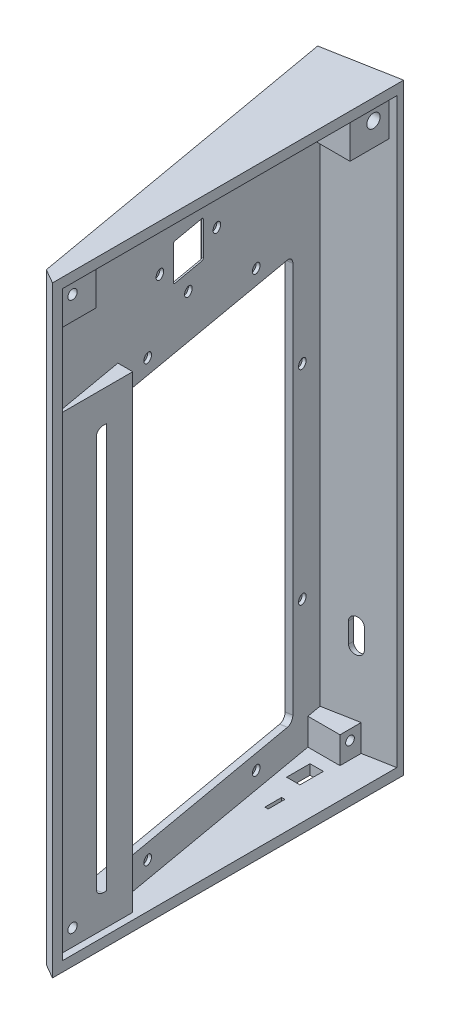
SolidWorks part; units mm, degrees
ref_plane "前视基准面" through (0, 0, 0) normal (0, 0, 1) x (1, 0, 0)
ref_plane "上视基准面" through (0, 0, 0) normal (0, 1, 0) x (1, 0, 0)
ref_plane "右视基准面" through (0, 0, 0) normal (1, 0, 0) x (0, 0, -1)
other "Configuration Table"
sketch "草图1" plane through (0, 0, 0) normal (0, 1, 0) x (1, 0, 0)
  line L0 (82.9035, -37.3993) -> (82.9035, -142.3993)
  line L1 (82.9035, -142.3993) -> (78.5734, -139.8993)
  line L2 (78.5734, -139.8993) -> (61.2086, -41.4185)
  line L3 (61.2086, -41.4185) -> (82.9035, -37.3993)
  dimension "D1" = 100
  dimension "D2" = 105
  dimension "D3" = 5
  dimension "D4" = 170
  dimension "D5" = 60
  dimension "D6" = 90.496
  dimension "D7" = 79.504
extrude "凸台-拉伸1" add sketch "草图1" along normal blind 180
sketch "草图5" plane through (52.2799, 0, -9.2184) normal (-0.9848, 0, 0.1736) x (0.1736, 0, 0.9848)
  line L0 (51.418, 180) -> (51.418, 0) construction
  line L1 (139.418, 12.5) -> (63.418, 12.5)
  line L2 (139.418, 12.5) -> (139.418, 133.5)
  line L3 (139.418, 133.5) -> (63.418, 133.5)
  line L4 (63.418, 12.5) -> (63.418, 133.5)
  line L5 (151.418, 180) -> (151.418, 0) construction
  line L6 (51.418, 0) -> (151.418, 0) construction
  dimension "D1" = 76
  dimension "D2" = 121
  dimension "D3" = 12
  dimension "D4" = 12
  dimension "D5" = 12.5
extrude "切除-拉伸2" cut sketch "草图5" against normal blind 2
sketch "草图7" plane through (82.9035, 0, 0) normal (1, 0, 0) x (0, 0, -1)
  line L8 (-139.3993, 3) -> (-40.3993, 3)
  line L9 (-40.3993, 3) -> (-40.3993, 177)
  line L10 (-40.3993, 177) -> (-139.3993, 177)
  line L11 (-139.3993, 177) -> (-139.3993, 3)
  line L12 (-139.3993, 3) -> (-40.3993, 3)
  line L13 (-40.3993, 3) -> (-40.3993, 177)
  line L14 (-40.3993, 177) -> (-139.3993, 177)
  line L15 (-139.3993, 177) -> (-139.3993, 3)
  dimension "D1" = 3
extrude "切除-拉伸3" cut sketch "草图7" against normal up to surface (19.8438 mm away) up to face at (71.8606, 73, 90.3116)
sketch "草图10" plane through (54.2496, 0, -9.5657) normal (0.9848, 0, -0.1736) x (-0.1736, 0, -0.9848)
  line L1 (-63.418, 12.5) -> (-59.918, 12.5) construction
  line L2 (-63.418, 12.5) -> (-63.418, 42.5) construction
  line L3 (-63.418, 42.5) -> (-59.918, 42.5) construction
  line L4 (-59.918, 12.5) -> (-59.918, 42.5) construction
  line L5 (-63.418, 133.5) -> (-59.918, 133.5) construction
  line L6 (-63.418, 133.5) -> (-63.418, 103.5) construction
  line L7 (-63.418, 103.5) -> (-59.918, 103.5) construction
  line L8 (-59.918, 133.5) -> (-59.918, 103.5) construction
  circle A0 centre (-59.918, 103.5) radius 1.4
  circle A1 centre (-59.918, 42.5) radius 1.4
  dimension "D1" = 30
  dimension "D2" = 30
  dimension "D3" = 3.5
  dimension "D4" = 3.5
extrude "切除-拉伸5" cut sketch "草图10" against normal blind 1
sketch "草图11" plane through (54.2496, 0, -9.5657) normal (0.9848, 0, -0.1736) x (-0.1736, 0, -0.9848)
  line L0 (-76.918, 8) -> (-116.918, 8) construction
  line L1 (-63.418, 133.5) -> (-76.918, 133.5) construction
  line L2 (-63.418, 133.5) -> (-63.418, 138) construction
  line L3 (-63.418, 138) -> (-76.918, 138) construction
  line L4 (-76.918, 133.5) -> (-76.918, 138) construction
  line L5 (-63.418, 12.5) -> (-76.918, 12.5) construction
  line L6 (-63.418, 12.5) -> (-63.418, 8) construction
  line L7 (-63.418, 8) -> (-76.918, 8) construction
  line L8 (-76.918, 12.5) -> (-76.918, 8) construction
  line L9 (-76.918, 138) -> (-116.918, 138) construction
  circle A0 centre (-116.918, 138) radius 1.4
  circle A1 centre (-76.918, 138) radius 1.4
  circle A2 centre (-116.918, 8) radius 1.4
  circle A3 centre (-76.918, 8) radius 1.4
  dimension "D1" = 13.5
  dimension "D2" = 4.5
  dimension "D3" = 13.5
  dimension "D4" = 4.5
  dimension "D5" = 40
  dimension "D6" = 40
extrude "切除-拉伸6" cut sketch "草图11" against normal blind 1
sketch "草图12" plane through (82.9035, 0, 0) normal (1, 0, 0) x (0, 0, -1)
  line L1 (-139.3993, 3) -> (-116.3993, 3)
  line L2 (-139.3993, 3) -> (-139.3993, 143)
  line L3 (-139.3993, 143) -> (-116.3993, 143)
  line L4 (-116.3993, 3) -> (-116.3993, 143)
  line L6 (-127.7343, 133.5) -> (-52.8889, 133.5) construction
  dimension "D1" = 9.5
  dimension "D2" = 23
extrude "凸台-拉伸3" add sketch "草图12" against normal up to surface (2.3874 mm away) up to face at (67.3631, 138, 64.8051)
sketch "草图13" plane through (54.2496, 0, -9.5657) normal (-0.9848, 0, 0.1736) x (0.1736, 0, 0.9848)
  line L4 (127.9081, 12.5) -> (139.418, 12.5)
  line L5 (139.418, 12.5) -> (139.418, 133.5)
  line L6 (139.418, 133.5) -> (127.9081, 133.5)
  line L7 (127.9081, 133.5) -> (127.9081, 12.5)
  line L8 (127.9081, 12.5) -> (139.418, 12.5)
  line L9 (139.418, 12.5) -> (139.418, 133.5)
  line L10 (139.418, 133.5) -> (127.9081, 133.5)
  line L11 (127.9081, 133.5) -> (127.9081, 12.5)
  dimension "D1" = 0
extrude "切除-拉伸7" cut sketch "草图13" against normal blind 2
sketch "草图14" plane through (52.2799, 0, -9.2184) normal (-0.9848, 0, 0.1736) x (0.1736, 0, 0.9848)
  line L0 (51.418, 180) -> (51.418, 0) construction
  line L1 (96.418, 151.5) -> (107.418, 151.5)
  line L2 (96.418, 151.5) -> (96.418, 162.5)
  line L3 (96.418, 162.5) -> (107.418, 162.5)
  line L4 (107.418, 151.5) -> (107.418, 162.5)
  line L5 (139.418, 133.5) -> (63.418, 133.5) construction
  line L6 (51.418, 180) -> (151.418, 180) construction
  dimension "D1" = 11
  dimension "D2" = 11
  dimension "D3" = 45
  dimension "D4" = 18
  dimension "D5" = 17.5
extrude "切除-拉伸8" cut sketch "草图14" against normal blind 2
sketch "草图17" plane through (9.4497, 0, 51.0074) normal (-0.1822, 0, -0.9833) x (-0.9833, 0, 0.1822)
  line L1 (-74.7037, 180) -> (-52.6396, 180)
  line L2 (-74.7037, 180) -> (-74.7037, 0)
  line L3 (-74.7037, 0) -> (-52.6396, 0)
  line L4 (-52.6396, 180) -> (-52.6396, 0)
extrude "凸台-拉伸9" add sketch "草图17" against normal blind 2
sketch "草图18" plane through (0, 0, 0) normal (0, -1, 0) x (1, 0, 0)
  line L0 (82.9035, 39.4333) -> (82.9035, 37.3993)
  line L1 (83.2679, 39.3658) -> (82.9035, 39.4333) construction
  line L2 (83.2679, 39.3658) -> (82.9035, 37.3993) construction
  line L3 (83.2679, 39.3658) -> (82.9035, 37.3993)
  line L4 (83.2679, 39.3658) -> (82.9035, 39.4333)
extrude "切除-拉伸9" cut sketch "草图18" against normal up to surface (180 mm away) up to face at (78.6267, 180, 73.3192)
sketch "草图19" plane through (0, 3, 0) normal (0, 1, 0) x (1, 0, 0)
  line L0 (82.9035, -40.3993) -> (82.9035, -36.7908) construction
  line L1 (77.596, -40.4166) -> (82.9035, -39.4333)
  line L2 (63.5225, -43.0238) -> (77.6894, -40.3993) construction
  line L3 (82.9035, -39.4333) -> (82.9035, -40.3993)
  line L4 (82.9035, -40.3993) -> (77.596, -40.4166)
extrude "切除-拉伸10" cut sketch "草图19" along normal up to surface (174 mm away) up to face at (77.507, 177, 80.5242)
sketch "草图20" plane through (82.9035, 0, 0) normal (1, 0, 0) x (0, 0, -1)
  line L1 (-139.3993, 143) -> (-116.3993, 143)
  line L2 (-139.3993, 143) -> (-139.3993, 3)
  line L3 (-139.3993, 3) -> (-116.3993, 3)
  line L4 (-116.3993, 143) -> (-116.3993, 3)
extrude "切除-拉伸11" cut sketch "草图20" against normal blind 2
sketch "草图21" plane through (54.2496, 0, -9.5657) normal (0.9848, 0, -0.1736) x (-0.1736, 0, -0.9848)
  line L0 (-107.418, 157) -> (-112.418, 157) construction
  line L1 (-107.418, 151.5) -> (-107.418, 162.5) construction
  line L2 (-101.918, 162.5) -> (-101.918, 167.5) construction
  line L3 (-107.418, 162.5) -> (-96.418, 162.5) construction
  line L4 (-96.418, 157) -> (-91.418, 157) construction
  line L5 (-96.418, 162.5) -> (-96.418, 151.5) construction
  line L6 (-101.918, 151.5) -> (-101.918, 146.5) construction
  line L7 (-96.418, 151.5) -> (-107.418, 151.5) construction
  circle A0 centre (-112.418, 157) radius 1.4
  circle A1 centre (-91.418, 157) radius 1.4
  circle A2 centre (-101.918, 146.5) radius 1.4
  circle A3 centre (-101.918, 167.5) radius 1.4
  dimension "D1" = 5
extrude "切除-拉伸12" cut sketch "草图21" against normal blind 1
sketch "草图23" plane through (80.9035, 0, 0) normal (1, 0, 0) x (0, 0, -1)
  line L0 (-51.4333, 8) -> (-51.4333, 26.4031) construction
  line L1 (-139.3993, 3) -> (-127.3993, 3)
  line L2 (-139.3993, 3) -> (-139.3993, 15)
  line L3 (-139.3993, 15) -> (-127.3993, 15)
  line L4 (-127.3993, 3) -> (-127.3993, 15)
  line L5 (-39.4333, 177) -> (-139.3993, 177) construction
  line L11 (-51.4333, 165) -> (-39.4333, 165)
  line L12 (-51.4333, 165) -> (-51.4333, 177)
  line L13 (-51.4333, 177) -> (-39.4333, 177)
  line L14 (-39.4333, 165) -> (-39.4333, 177)
  line L15 (-127.3993, 8) -> (-127.3993, 23.4787) construction
  line L17 (-127.3993, 165) -> (-139.3993, 165)
  line L18 (-127.3993, 165) -> (-127.3993, 177)
  line L19 (-127.3993, 177) -> (-139.3993, 177)
  line L20 (-139.3993, 165) -> (-139.3993, 177)
  dimension "D1" = 12
  dimension "D2" = 12
  dimension "D5" = 0
  dimension "D6" = 12
  dimension "D7" = 12
  dimension "D8" = 12
  dimension "D9" = 12
  dimension "D11" = 0
extrude "凸台-拉伸10" add sketch "草图23" against normal up to surface (0.3874 mm away) up to face at (73.5276, 157, 99.7657)
fillet "圆角4" radius 2 5 edges at (64.2772, 133.5, 53.0625) (78.4592, 133.5, 127.7343) (64.2772, 12.5, 53.0625) (77.4744, 12.5, 127.9079) (80.394, 12.5, 127.3931)
sketch "草图26" plane through (0, 177, 0) normal (0, 1, 0) x (1, 0, 0)
  line L3 (63.1752, -41.0542) -> (71.9242, -39.4333)
  line L4 (71.9242, -39.4333) -> (62.8894, -39.4333)
  line L5 (62.8894, -39.4333) -> (63.1752, -41.0542)
  line L6 (63.1752, -41.0542) -> (71.9242, -39.4333)
  line L7 (71.9242, -39.4333) -> (62.8894, -39.4333)
  line L8 (62.8894, -39.4333) -> (63.1752, -41.0542)
  dimension "D1" = 0
extrude "切除-拉伸15" cut sketch "草图26" against normal up to next
sketch "草图27" plane through (82.9035, 0, 0) normal (1, 0, 0) x (0, 0, -1)
  line L1 (-39.4333, 3) -> (-47.4333, 3)
  line L2 (-39.4333, 3) -> (-39.4333, 11)
  line L3 (-39.4333, 11) -> (-47.4333, 11)
  line L4 (-47.4333, 3) -> (-47.4333, 11)
  dimension "D1" = 8
  dimension "D2" = 8
extrude "凸台-拉伸11" add sketch "草图27" against normal up to surface (18.6035 mm away) up to face at (73.5276, 157, 99.7657)
sketch "草图28" plane through (82.9035, 0, 0) normal (1, 0, 0) x (0, 0, -1)
  line L1 (-47.4333, 3) -> (-39.4333, 3)
  line L2 (-47.4333, 3) -> (-47.4333, 11)
  line L3 (-47.4333, 11) -> (-39.4333, 11)
  line L4 (-39.4333, 3) -> (-39.4333, 11)
extrude "切除-拉伸16" cut sketch "草图28" against normal blind 9
sketch "草图29" plane through (0, 11, 0) normal (0, -1, 0) x (1, 0, 0)
  line L3 (73.9035, 41.1006) -> (73.9035, 39.4333)
  line L4 (73.9035, 39.4333) -> (82.9035, 39.4333)
  line L5 (82.9035, 39.4333) -> (73.9035, 41.1006)
  line L6 (73.9035, 41.1006) -> (73.9035, 39.4333)
  line L7 (73.9035, 39.4333) -> (82.9035, 39.4333)
  line L11 (82.9035, 39.4333) -> (73.9035, 41.1006)
  dimension "D1" = 0
extrude "凸台-拉伸12" add sketch "草图29" along normal up to surface (8 mm away) up to face at (77.0227, 3, 85.6663)
sketch "草图30" plane through (0, 3, 0) normal (0, -1, 0) x (1, 0, 0)
  line L3 (71.9242, 39.4333) -> (63.1752, 41.0542)
  line L4 (63.1752, 41.0542) -> (62.8894, 39.4333)
  line L5 (62.8894, 39.4333) -> (71.9242, 39.4333)
  line L6 (71.9242, 39.4333) -> (63.1752, 41.0542)
  line L7 (63.1752, 41.0542) -> (62.8894, 39.4333)
  line L8 (62.8894, 39.4333) -> (71.9242, 39.4333)
  dimension "D1" = 0
extrude "切除-拉伸17" cut sketch "草图30" against normal up to next
sketch "草图31" plane through (0, 0, 0) normal (0, -1, 0) x (1, 0, 0)
  line L1 (82.9035, 37.3993) -> (68.9035, 37.3993) construction
  line L2 (82.9035, 37.3993) -> (82.9035, 51.3993) construction
  line L3 (82.9035, 51.3993) -> (68.9035, 51.3993) construction
  line L4 (68.9035, 37.3993) -> (68.9035, 51.3993) construction
  line L5 (68.9035, 51.3993) -> (72.9035, 51.3993)
  line L6 (68.9035, 51.3993) -> (68.9035, 58.3993)
  line L7 (68.9035, 58.3993) -> (72.9035, 58.3993)
  line L8 (72.9035, 51.3993) -> (72.9035, 58.3993)
  dimension "D1" = 14
  dimension "D2" = 14
  dimension "D3" = 7
  dimension "D4" = 4
extrude "切除-拉伸18" cut sketch "草图31" against normal up to next
ref_plane "基准面1" through (0, 0, 37.3993) normal (0, 0, -1) x (-1, 0, 0)
ref_plane "基准面2" through (0, 0, 39.7193) normal (0, 0, -1) x (-1, 0, 0)
sketch "草图32" plane through (0, 0, 39.7193) normal (0, 0, -1) x (-1, 0, 0)
  line L0 (-72.7086, 36) -> (-72.7086, 30) construction
  line L1 (-70.7086, 36) -> (-70.7086, 30)
  line L2 (-74.7086, 36) -> (-74.7086, 30)
  line L3 (-82.9035, 180) -> (-61.2086, 180) construction
  line L4 (-61.2086, 180) -> (-61.2086, 0) construction
  arc A0 (-70.7086, 36) -> (-74.7086, 36) centre (-72.7086, 36) ccw
  arc A1 (-74.7086, 30) -> (-70.7086, 30) centre (-72.7086, 30) ccw
  point P2 (-72.7086, 33)
  point P9 (-72.7086, 28)
  point P10 (-72.7086, 38)
  dimension "D1" = 147
  dimension "D2" = 10
  dimension "D3" = 4
  dimension "D4" = 9.5
extrude "切除-拉伸23" cut sketch "草图32" against normal up to surface (1.9733 mm away) up to face at (75.3083, 89, 40.8404)
ref_plane "基准面4" through (0, 0, 40.2193) normal (0, 0, -1) x (-1, 0, 0)
sketch "草图35" plane through (0, 0, 40.2193) normal (0, 0, -1) x (-1, 0, 0)
  line L0 (-74.7086, 36) -> (-74.7086, 30) construction
  line L1 (-76.7086, 41) -> (-68.7086, 41)
  line L2 (-76.7086, 41) -> (-76.7086, 25)
  line L3 (-76.7086, 25) -> (-68.7086, 25)
  line L4 (-68.7086, 41) -> (-68.7086, 25)
  line L5 (-70.7086, 30) -> (-70.7086, 36) construction
  arc A0 (-70.7086, 36) -> (-74.7086, 36) centre (-72.7086, 36) ccw construction
  arc A1 (-74.7086, 30) -> (-70.7086, 30) centre (-72.7086, 30) ccw construction
  dimension "D1" = 5
  dimension "D2" = 5
  dimension "D3" = 2
  dimension "D4" = 2
extrude "切除-拉伸25" cut sketch "草图35" along normal up to surface (0.1902 mm away) up to face at (72.0561, 90, 39.4089)
fillet "圆角5" radius 0.5 4 edges at (76.7086, 25, 39.3831) (76.7086, 41, 39.3831) (68.7086, 25, 40.1241) (68.7086, 41, 40.1241)
sketch "草图36" plane through (0, 0, 0) normal (0, -1, 0) x (1, 0, 0)
  line L1 (82.9035, 37.3993) -> (74.4035, 37.3993) construction
  line L2 (82.9035, 37.3993) -> (82.9035, 64.3993) construction
  line L3 (82.9035, 64.3993) -> (74.4035, 64.3993) construction
  line L4 (74.4035, 37.3993) -> (74.4035, 64.3993) construction
  line L5 (74.4035, 64.3993) -> (73.4035, 64.3993)
  line L6 (74.4035, 64.3993) -> (74.4035, 69.3993)
  line L7 (74.4035, 69.3993) -> (73.4035, 69.3993)
  line L8 (73.4035, 64.3993) -> (73.4035, 69.3993)
  dimension "D1" = 8.5
  dimension "D2" = 27
  dimension "D3" = 1
  dimension "D4" = 5
extrude "切除-拉伸26" cut sketch "草图36" against normal up to next
sketch "草图37" plane through (0, 0, 0) normal (0, -1, 0) x (1, 0, 0)
  line L0 (73.4035, 66.8993) -> (74.4035, 66.8993) construction
  line L1 (73.4035, 69.3993) -> (73.4035, 64.3993) construction
  line L2 (74.4035, 64.3993) -> (74.4035, 69.3993) construction
  line L3 (73.9035, 64.3993) -> (73.9035, 69.3993) construction
  line L4 (73.4035, 64.3993) -> (74.4035, 64.3993) construction
  line L5 (74.4035, 69.3993) -> (73.4035, 69.3993) construction
  line L7 (74.9035, 69.8993) -> (72.9035, 69.8993)
  line L8 (74.9035, 69.8993) -> (74.9035, 63.8993)
  line L9 (74.9035, 63.8993) -> (72.9035, 63.8993)
  line L10 (72.9035, 69.8993) -> (72.9035, 63.8993)
  line L11 (74.9035, 69.8993) -> (72.9035, 63.8993) construction
  line L12 (74.9035, 63.8993) -> (72.9035, 69.8993) construction
  point P12 (73.9035, 66.8993)
  dimension "D1" = 6
  dimension "D2" = 2
extrude "切除-拉伸27" cut sketch "草图37" against normal blind 1
sketch "草图38" plane through (73.9035, 0, 0) normal (1, 0, 0) x (0, 0, -1)
  line L0 (-47.4333, 3) -> (-41.1006, 3) construction
  line L1 (-47.4333, 11) -> (-44.4333, 11) construction
  line L2 (-47.4333, 11) -> (-47.4333, 8) construction
  line L3 (-47.4333, 8) -> (-44.4333, 8) construction
  line L4 (-44.4333, 11) -> (-44.4333, 8) construction
  line L5 (-47.4333, 11) -> (-47.4333, 3) construction
  circle A0 centre (-44.4333, 8) radius 1.3
  dimension "D1" = 5
  dimension "D2" = 3
extrude "切除-拉伸28" cut sketch "草图38" against normal blind 3 contours A0
sketch "草图39" plane through (80.9035, 0, 0) normal (1, 0, 0) x (0, 0, -1)
  line L0 (-47.4333, 10.1358) -> (-47.4333, 2.8866) construction
  line L1 (-51.4333, 177) -> (-51.4333, 165) construction
  line L4 (-39.8038, 177) -> (-51.4333, 177) construction
  line L5 (-47.4333, 169) -> (-39.8038, 169) construction
  line L6 (-47.4333, 169) -> (-47.4333, 177) construction
  line L7 (-47.4333, 177) -> (-39.8038, 177) construction
  line L8 (-39.8038, 169) -> (-39.8038, 177) construction
  line L10 (-47.4333, 169) -> (-44.4333, 169) construction
  line L11 (-47.4333, 169) -> (-47.4333, 172) construction
  line L12 (-47.4333, 172) -> (-44.4333, 172) construction
  line L13 (-44.4333, 169) -> (-44.4333, 172) construction
  circle A0 centre (-44.4333, 172) radius 2
  dimension "D4" = 7
  dimension "D1" = 8
  dimension "D2" = 3
  dimension "D3" = 3
  dimension "D5" = 5
extrude "切除-拉伸30" cut sketch "草图39" against normal blind 3
sketch "草图40" plane through (80.9035, 0, 0) normal (1, 0, 0) x (0, 0, -1)
  line L1 (-127.3993, 177) -> (-131.3993, 177) construction
  line L2 (-127.3993, 177) -> (-127.3993, 171) construction
  line L3 (-127.3993, 171) -> (-131.3993, 171) construction
  line L4 (-131.3993, 177) -> (-131.3993, 171) construction
  line L5 (-131.3993, 171) -> (-134.3993, 171) construction
  line L6 (-131.3993, 171) -> (-131.3993, 172) construction
  line L7 (-131.3993, 172) -> (-134.3993, 172) construction
  line L8 (-134.3993, 171) -> (-134.3993, 172) construction
  line L9 (-139.3993, 3) -> (-134.3993, 3) construction
  line L10 (-139.3993, 3) -> (-139.3993, 8) construction
  line L11 (-139.3993, 8) -> (-134.3993, 8) construction
  line L12 (-134.3993, 3) -> (-134.3993, 8) construction
  circle A0 centre (-134.3993, 172) radius 1.4
  circle A1 centre (-134.3993, 8) radius 1.4
  dimension "D5" = 5
  dimension "D1" = 6
  dimension "D2" = 4
  dimension "D3" = 3
  dimension "D4" = 1
  dimension "D6" = 5
extrude "切除-拉伸31" cut sketch "草图40" against normal blind 2
sketch "草图42" plane through (54.2496, 0, -9.5657) normal (-0.9848, 0, 0.1736) x (0.1736, 0, 0.9848)
  line L3 (139.0778, 15) -> (139.0778, 13.3842)
  line L4 (139.418, 14.5) -> (139.418, 15)
  line L5 (139.418, 15) -> (139.0778, 15)
  line L6 (139.0778, 15) -> (139.0778, 13.3842)
  line L7 (139.418, 14.5) -> (139.418, 15)
  line L8 (139.418, 15) -> (139.0778, 15)
  arc A1 (139.0778, 13.3842) -> (139.418, 14.5) centre (137.418, 14.5) ccw
  arc A2 (139.0778, 13.3842) -> (139.418, 14.5) centre (137.418, 14.5) ccw
  dimension "D1" = 0
extrude "切除-拉伸34" cut sketch "草图42" against normal up to surface (2 mm away) up to face at (79.6913, 73, 123.2038)
chamfer "倒角1" distance 2 distance2 1.5 4 edges at (69.9778, 151.5, 91.1513) (69.0228, 157, 85.7348) (69.9778, 162.5, 91.1513) (70.9329, 157, 96.5677) first distance on face at (69.9778, 157, 91.1513)
fillet "圆角6" radius 0.5 4 edges at (72.6563, 151.5, 96.2638) (72.6563, 162.5, 96.2638) (70.7462, 162.5, 85.431) (70.7462, 151.5, 85.431)
sketch "草图43" plane through (56.2192, 0, -9.913) normal (-0.9848, 0, 0.1736) x (0.1736, 0, 0.9848)
  line L4 (139.418, 14.5) -> (139.418, 131.5)
  line L5 (137.418, 133.5) -> (128.2608, 133.5)
  line L6 (128.2608, 133.5) -> (128.2608, 12.5)
  line L7 (128.2608, 12.5) -> (137.418, 12.5)
  line L8 (139.418, 14.5) -> (139.418, 131.5)
  line L9 (137.418, 133.5) -> (128.2608, 133.5)
  line L10 (128.2608, 133.5) -> (128.2608, 12.5)
  line L11 (128.2608, 12.5) -> (137.418, 12.5)
  arc A2 (139.418, 131.5) -> (137.418, 133.5) centre (137.418, 131.5) ccw
  arc A3 (137.418, 12.5) -> (139.418, 14.5) centre (137.418, 14.5) ccw
  arc A4 (139.418, 131.5) -> (137.418, 133.5) centre (137.418, 131.5) ccw
  arc A5 (137.418, 12.5) -> (139.418, 14.5) centre (137.418, 14.5) ccw
  dimension "D1" = 0
extrude "切除-拉伸35" cut sketch "草图43" against normal blind 1
